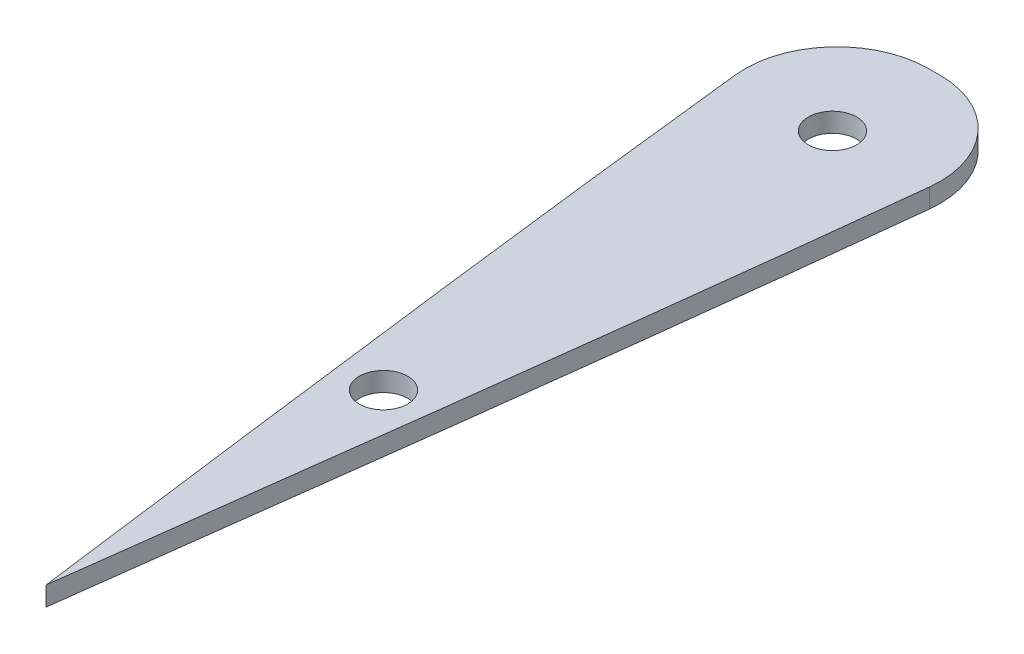
SolidWorks part; units mm, degrees
material "Balsa"
ref_plane "Front Plane" through (0, 0, 0) normal (0, 0, 1) x (1, 0, 0)
ref_plane "Top Plane" through (0, 0, 0) normal (0, 1, 0) x (1, 0, 0)
ref_plane "Right Plane" through (0, 0, 0) normal (1, 0, 0) x (0, 0, -1)
sketch "Sketch1" plane through (0, 0, 0) normal (0, 1, 0) x (1, 0, 0)
  line L0 (1.1081, 1.7265) -> (-45.0799, 1.7265) construction
  line L1 (-45.0799, 1.7265) -> (-45.0799, -11.2275) construction
  line L2 (-45.0799, -11.2275) -> (43.7517, -11.2275) construction
  line L3 (1.1081, 103.3269) -> (1.1081, -99.8738) construction
  line L4 (-45.0799, -11.2275) -> (-45.0799, -20.7525) construction
  line L5 (-28.2049, 1.7265) -> (-28.2049, -3.6075) construction
  line L6 (-9.9553, -3.6075) -> (-6.7697, -3.6075)
  line L7 (-28.2049, -3.6075) -> (-9.9553, -3.6075) construction
  line L8 (-6.7697, -3.6075) -> (1.1081, -3.6075) construction
  line L9 (8.9859, -3.6075) -> (12.1715, -3.6075)
  line L10 (12.1715, -3.6075) -> (18.1346, -3.6075) construction
  line L11 (12.1715, -3.6075) -> (18.1346, -3.6075) construction
  line L12 (18.1346, -3.6075) -> (29.3788, -3.6075) construction
  line L13 (1.1081, -3.6075) -> (8.9859, -3.6075) construction
  line L14 (-6.7697, -3.6075) -> (8.9859, -3.6075)
  circle A0 centre (1.1081, -11.3265) radius 1.9844 construction
  circle A1 centre (1.1081, -11.3265) radius 1.9844
  spline S0 degree 3 poles (1.1081, -99.8738) (4.5273, -73.5318) (7.9866, -47.1872) (10.6029, -20.7525) knots 0 0 0 0 0.38497 0.38497 0.38497 0.38497
  spline S3 degree 3 poles (1.1081, -99.8738) (-2.3112, -73.5318) (-5.7704, -47.1872) (-8.3867, -20.7525) knots 0 0 0 0 0.38497 0.38497 0.38497 0.38497
  spline S4 degree 3 poles (10.6029, -20.7525) (11.1, -15.7302) (11.6306, -10.016) (12.114, -4.2968) (12.1715, -3.6075) knots 0.38497 0.38497 0.38497 0.38497 0.458109 0.468132 0.468132 0.468132 0.468132
  spline S5 degree 3 poles (-8.3867, -20.7525) (-8.8838, -15.7302) (-9.4144, -10.016) (-9.8978, -4.2968) (-9.9553, -3.6075) knots 0.38497 0.38497 0.38497 0.38497 0.458109 0.468132 0.468132 0.468132 0.468132
  spline S8 degree 3 poles (12.1715, -3.6075) (12.8364, 4.367) (14.1908, 23.6726) (14.0058, 48.0803) (13.0188, 67.5796) (11.3266, 78.9472) (9.5869, 86.9693) (8.1237, 93.6397) (6.4505, 97.563) (4.8164, 101.3994) (2.3437, 102.5279) (1.1081, 103.3269) knots 0.468132 0.468132 0.468132 0.468132 0.584075 0.748482 0.821537 0.866809 0.914778 0.94069 0.965303 0.976863 1 1 1 1 construction
  spline S9 degree 3 poles (1.1081, 99.6196) (1.2739, 99.518) (1.6209, 99.2976) (2.0134, 99.0137) (2.3095, 98.7539) (2.4667, 98.5788) (2.6076, 98.3713) (2.8163, 97.9774) (3.0534, 97.4394) (3.4327, 96.5453) (3.8774, 95.496) (4.541, 93.8448) (5.2023, 91.9048) (5.8236, 89.3366) (6.4213, 86.5662) (7.0145, 83.8293) (7.767, 80.1951) (8.6007, 75.6781) (9.6391, 68.4081) (10.3034, 59.2354) (10.6788, 47.9926) (10.8555, 36.7918) (10.7415, 25.5951) (10.3009, 14.4244) (9.6564, 4.6878) (9.1767, -1.3266) (8.9859, -3.6075) knots 0.118744 0.118744 0.118744 0.118744 0.122149 0.125554 0.12896 0.132365 0.13577 0.139175 0.142581 0.145986 0.152796 0.159607 0.173228 0.186849 0.20047 0.214091 0.227711 0.254953 0.282195 0.336679 0.391163 0.445646 0.50013 0.554614 0.609098 0.642376 0.642376 0.642376 0.642376 construction
  spline S10 degree 3 poles (-7.1984, 1.7265) (-7.237, 2.2289) (-7.5577, 6.4638) (-8.0847, 14.4244) (-8.5253, 25.5951) (-8.6393, 36.7918) (-8.4626, 47.9926) (-8.0872, 59.2354) (-7.4229, 68.4081) (-6.3845, 75.6781) (-5.5508, 80.1951) (-4.7983, 83.8293) (-4.2051, 86.5662) (-3.6074, 89.3366) (-2.9861, 91.9048) (-2.3248, 93.8448) (-1.6612, 95.496) (-1.2165, 96.5453) (-0.8372, 97.4394) (-0.6001, 97.9774) (-0.3914, 98.3713) (-0.2505, 98.5788) (-0.0933, 98.7539) (0.2028, 99.0137) (0.5953, 99.2976) (0.9423, 99.518) (1.1081, 99.6196) knots 0.492798 0.492798 0.492798 0.492798 0.50013 0.554614 0.609098 0.663581 0.718065 0.772549 0.827033 0.854275 0.881516 0.895137 0.908758 0.922379 0.936 0.949621 0.956432 0.963242 0.966647 0.970053 0.973458 0.976863 0.980268 0.983674 0.987079 0.990484 0.990484 0.990484 0.990484 construction
  spline S11 degree 3 poles (-10.3826, 1.7265) (-10.8572, 7.9268) (-11.9611, 25.4575) (-11.7896, 48.0803) (-10.8026, 67.5796) (-9.1104, 78.9472) (-7.3707, 86.9693) (-5.9075, 93.6397) (-4.2343, 97.563) (-2.6002, 101.3994) (-0.1276, 102.5279) (1.1081, 103.3269) knots 0.493976 0.493976 0.493976 0.493976 0.584075 0.748482 0.821537 0.866809 0.914778 0.94069 0.965303 0.976863 1 1 1 1 construction
  spline S12 degree 3 poles (-9.9553, -3.6075) (-10.1035, -1.8299) (-10.2465, -0.0519) (-10.3826, 1.7265) knots 0.468132 0.468132 0.468132 0.468132 0.493976 0.493976 0.493976 0.493976 construction
  spline S13 degree 3 poles (-6.7697, -3.6075) (-6.9185, -1.8292) (-7.0618, -0.0511) (-7.1984, 1.7265) knots 0.466852 0.466852 0.466852 0.466852 0.492798 0.492798 0.492798 0.492798 construction
  dimension "D4" = 3.9688
  dimension "D1" = 12.954
  dimension "D2" = 9.525
  dimension "D3" = 5.334
extrude "Boss-Extrude1" add sketch "Sketch1" along normal blind 169.8727
sketch "Sketch2" plane through (0, 169.8727, 0) normal (0, 1, 0) x (1, 0, 0)
  line L1 (-9.9553, -3.6075) -> (25.8085, -3.6075)
  line L2 (-9.9553, -3.6075) -> (-9.9553, -26.3125)
  line L3 (-9.9553, -26.3125) -> (25.8085, -26.3125)
  line L4 (25.8085, -3.6075) -> (25.8085, -26.3125)
  circle A0 centre (1.1081, -11.3265) radius 1.9844 construction
  dimension "D1" = 14.986
extrude "Cut-Extrude1" cut sketch "Sketch2" against normal blind 23.0581
extrude "Cut-Extrude2" cut sketch "Sketch2<2>" along normal blind 23.0581 from surface starting at face at (-1.1046, 0, 29.7187)
sketch "Sketch2<2>" plane through (0, 169.8727, 0) normal (0, 1, 0) x (1, 0, 0) same geometry as "Sketch2"
fillet "Fillet1" radius 7.62 6 edges at (-7.8242, 11.5291, 26.3125) (10.0403, 11.5291, 26.3125) (12.1715, 84.9363, 3.6075) (-7.8242, 158.3436, 26.3125) (10.0403, 158.3436, 26.3125)
sketch "Sketch6" plane through (0, 0, 0) normal (0, -1, 0) x (1, 0, 0)
  line L0 (1.1081, 3.6075) -> (1.1081, 99.8738) construction
  line L1 (-1.6395, 3.6075) -> (3.8557, 3.6075) construction
  line L2 (-6.9254, 34.7606) -> (9.1416, 34.7606) construction
  circle A0 centre (1.1081, 71.9338) radius 2
  circle A1 centre (1.1081, 34.7606) radius 2
  dimension "D1" = 4
  dimension "D2" = 27.94
extrude "Cut-Extrude3" cut sketch "Sketch6" against normal through all both and the other way through all
sketch "Sketch7" plane through (0, 0, 0) normal (1, 0, 0) x (0, 0, -1)
  line L0 (-3.6075, 146.8145) -> (-3.6075, 23.0581) construction
  line L1 (-99.8738, 0) -> (-3.6075, 0)
  line L2 (-99.8738, 0) -> (-99.8738, 159.2848)
  line L3 (-99.8738, 159.2848) -> (-3.6075, 159.2848)
  line L4 (-3.6075, 0) -> (-3.6075, 159.2848)
  line L6 (-99.8738, 169.8727) -> (-3.6075, 169.8727)
  line L7 (-99.8738, 169.8727) -> (-99.8738, 160.8723)
  line L8 (-99.8738, 160.8723) -> (-3.6075, 160.8723)
  line L9 (-3.6075, 169.8727) -> (-3.6075, 160.8723)
  dimension "D2" = 1.5875
extrude "Cut-Extrude4" cut sketch "Sketch7" against normal through all both and the other way through all
